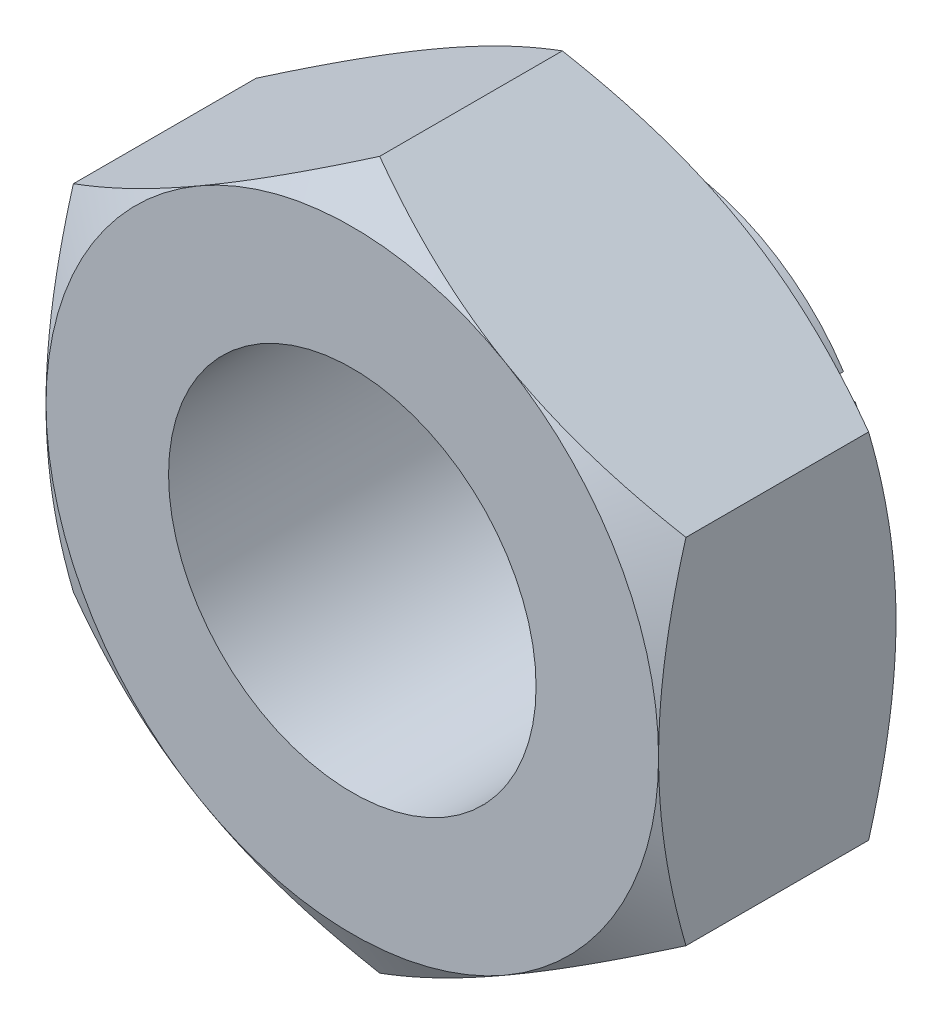
SolidWorks part; units mm, degrees
ref_plane "Front Plane" through (0, 0, 0) normal (0, 0, 1) x (1, 0, 0)
ref_plane "Top Plane" through (0, 0, 0) normal (0, 1, 0) x (1, 0, 0)
ref_plane "Right Plane" through (0, 0, 0) normal (1, 0, 0) x (0, 0, -1)
sketch "Sketch1" plane through (0, 0, 0) normal (0, 0, 1) x (1, 0, 0)
  line L1 (0, 5.7735) -> (-5, 2.8868)
  line L2 (-5, 2.8868) -> (-5, -2.8868)
  line L3 (-5, -2.8868) -> (0, -5.7735)
  line L4 (0, -5.7735) -> (5, -2.8868)
  line L5 (5, -2.8868) -> (5, 2.8868)
  line L6 (5, 2.8868) -> (0, 5.7735)
  circle A0 centre (0, 0) radius 5 construction
  dimension "Hex" = 10
extrude "Extrude1" add sketch "Sketch1" against normal blind 5
sketch "Sketch2" plane through (0, 0, 0) normal (0, 0, 1) x (1, 0, 0)
  circle A0 centre (0, 0) radius 5 construction
  circle A1 centre (0, 0) radius 5
extrude "Cut-Extrude1" cut sketch "Sketch2" against normal through all draft 60 flip side to cut
sketch "Sketch4" plane through (0, 0, 0) normal (0, 0, 1) x (1, 0, 0)
  circle A0 centre (0, 0) radius 3
  dimension "Thread Dia" = 6
extrude "Cut-Extrude3" cut sketch "Sketch4" against normal through all
sketch "Sketch5" [suppressed] plane through (0, 0, 0) normal (0, 0, 1) x (1, 0, 0)
  circle A0 centre (0, 0) radius 3 construction
  circle A1 centre (0, 0) radius 3
sketch "Sketch12" plane through (0, 0, -5) normal (0, 0, -1) x (-1, 0, 0)
  line L0 (0, 0) -> (5, 2.8868) construction
  circle A0 centre (0, 0) radius 3.6
  dimension "D1" = 7.2
extrude "Cut-Extrude10" cut sketch "Sketch12" against normal blind 1.125 flip side to cut
sketch "Sketch15" plane through (0, 0, -5) normal (0, 0, -1) x (-1, 0, 0)
  line L0 (0, 0) -> (0, -5.7735)
extrude "Cut-Extrude-Thin2" cut sketch "Sketch15" against normal offset from surface (0.617 mm away) 0.508 thin up to face at (0, 0, -3.875) thin type mid plane wall 0.381
pattern_circular "CirPattern1" count 6 over 360 of "Cut-Extrude-Thin2"
sketch "Sketch3" plane through (0, 0, -3.875) normal (0, 0, -1) x (-1, 0, 0)
  circle A1 centre (0, 0) radius 5
  circle A2 centre (0, 0) radius 5
  dimension "D1" = 0
extrude "Cut-Extrude2" cut sketch "Sketch3" against normal through all draft 60 flip side to cut
curve "Helix/Spiral1" [suppressed] pitch 1 height 6 turns 6 parameters "pitch"=1
sketch "Sketch9" [suppressed] plane through (0, 0, 0) normal (1, 0, 0) x (0, 0, -1)
  line L0 (-0.5, 2.3505) -> (-0.375, 2.3505)
  line L1 (-0.375, 2.3505) -> (0, 3)
  line L2 (-0.5, 2.3505) -> (-0.875, 3)
  line L3 (-0.875, 3) -> (0, 3)
  line L4 (-0.4375, 2.3505) -> (-0.4375, 3) construction
  line L5 (-0.6875, 2.6752) -> (-0.1875, 2.6752) construction
  line L6 (0, 3) -> (0, -3) construction
  dimension "D1" = 0.125
  dimension "D2" = 0.5
  dimension "D3" = 60
sweep "Sweep1" [suppressed] add profiles "Sketch9" path "Helix/Spiral1"
sketch "Sketch10" [suppressed] plane through (0, 0, 0) normal (0, 0, 1) x (1, 0, 0)
  line L6 (0, 5.7735) -> (-5, 2.8868)
  line L7 (-5, 2.8868) -> (-5, -2.8868)
  line L8 (-5, -2.8868) -> (0, -5.7735)
  line L9 (0, -5.7735) -> (5, -2.8868)
  line L10 (5, -2.8868) -> (5, 2.8868)
  line L11 (5, 2.8868) -> (0, 5.7735)
  line L12 (0, 5.7735) -> (-5, 2.8868)
  line L13 (-5, 2.8868) -> (-5, -2.8868)
  line L14 (-5, -2.8868) -> (0, -5.7735)
  line L15 (0, -5.7735) -> (5, -2.8868)
  line L16 (5, -2.8868) -> (5, 2.8868)
  line L17 (5, 2.8868) -> (0, 5.7735)
  dimension "D1" = 0
extrude "Cut-Extrude8" [suppressed] cut sketch "Sketch10" along normal through all
sketch "Sketch11" [suppressed] plane through (0, 0, -5) normal (0, 0, -1) x (-1, 0, 0)
  line L6 (5, 2.8868) -> (0, 5.7735)
  line L7 (5, -2.8868) -> (5, 2.8868)
  line L8 (0, -5.7735) -> (5, -2.8868)
  line L9 (-5, -2.8868) -> (0, -5.7735)
  line L10 (-5, 2.8868) -> (-5, -2.8868)
  line L11 (0, 5.7735) -> (-5, 2.8868)
  line L12 (5, 2.8868) -> (0, 5.7735)
  line L13 (5, -2.8868) -> (5, 2.8868)
  line L14 (0, -5.7735) -> (5, -2.8868)
  line L15 (-5, -2.8868) -> (0, -5.7735)
  line L16 (-5, 2.8868) -> (-5, -2.8868)
  line L17 (0, 5.7735) -> (-5, 2.8868)
  dimension "D1" = 0
extrude "Cut-Extrude9" [suppressed] cut sketch "Sketch11" along normal through all
sketch "Sketch7" [suppressed] plane through (0, 0, 0) normal (0, 0, 1) x (1, 0, 0)
  circle A1 centre (0, 0) radius 3
  circle A2 centre (0, 0) radius 3
  dimension "D1" = 0
extrude "Cut-Extrude6" [suppressed] cut sketch "Sketch7" against normal through all draft 45
sketch "Sketch8" [suppressed] plane through (0, 0, -5) normal (0, 0, -1) x (-1, 0, 0)
  circle A1 centre (0, 0) radius 3
  circle A3 centre (0, 0) radius 3
  dimension "D1" = 0
extrude "Cut-Extrude7" [suppressed] cut sketch "Sketch8" against normal through all draft 45
sketch "Sketch17" [suppressed] plane through (0, 0, 0) normal (0, 0, 1) x (1, 0, 0)
  circle A0 centre (0, 0) radius 3.01
  circle A1 centre (0, 0) radius 3
  circle A2 centre (0, 0) radius 3
  dimension "D1" = 0
  dimension "D2" = 0.01
extrude "Boss-Extrude1" [suppressed] add sketch "Sketch17" against normal blind 0.1
sketch "Sketch16" [suppressed] plane through (0, 0, -5) normal (0, 0, -1) x (-1, 0, 0)
  line L1 (0, 0) -> (0, -5.7735)
extrude "Cut-Extrude-Thin3" [suppressed] cut sketch "Sketch16" against normal offset from surface (0.625 mm away) 0.5 thin up to face at (-3.6, 0, -3.875) thin type mid plane wall 0.381
pattern_circular "CirPattern14" [suppressed] count 6 over 360 of bodies 126
ref_axis "Center Axis 1" through (0, 0, -5.4129) along (0, 0, 1)
equation "\"D2@Sketch9\" = \"pitch@Helix/Spiral1\"*.5"
equation "\"D3@Helix/Spiral1\" = \"pitch@Helix/Spiral1\"+\"Height@Extrude1\""
equation "\"D1@Sketch9\" = \"pitch@Helix/Spiral1\"*.125"
equation "\"D1@Sketch12\" = \"Thread Dia@Sketch4\"*1.2"
equation "\"D1@Cut-Extrude10\" = \"Height@Extrude1\"*.225"
